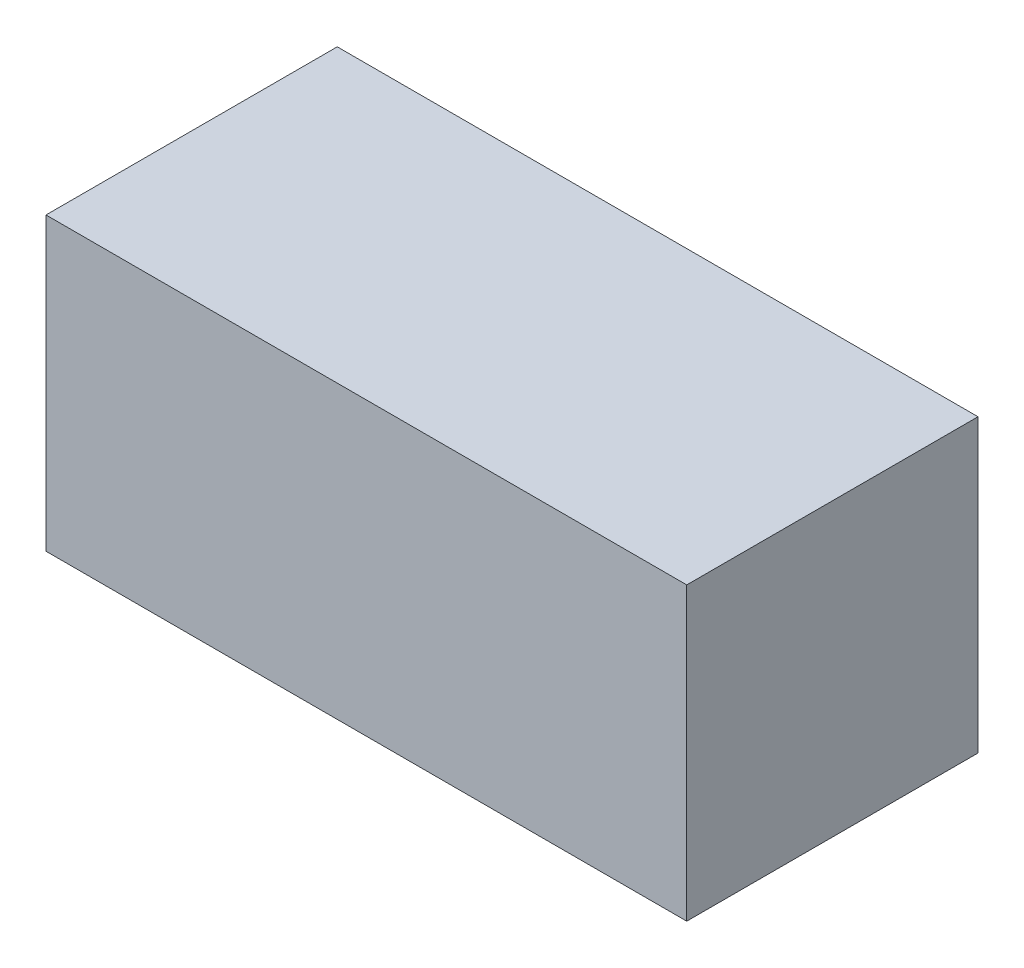
SolidWorks part; units mm, degrees
ref_plane "Front" through (0, 0, 0) normal (0, 0, 1) x (1, 0, 0)
ref_plane "Top" through (0, 0, 0) normal (0, 1, 0) x (1, 0, 0)
ref_plane "Right" through (0, 0, 0) normal (1, 0, 0) x (0, 0, -1)
sketch "Sketch1" plane through (0, 0, 0) normal (0, 0, 1) x (1, 0, 0)
  line L1 (-55, 25) -> (55, 25)
  line L2 (-55, 25) -> (-55, -25)
  line L3 (-55, -25) -> (55, -25)
  line L4 (55, 25) -> (55, -25)
  line L5 (-55, 25) -> (55, -25) construction
  line L6 (-55, -25) -> (55, 25) construction
  point P0 (0, 0)
  dimension "D1" = 50
  dimension "D2" = 110
extrude "Boss-Extrude1" add sketch "Sketch1" along normal blind 50
